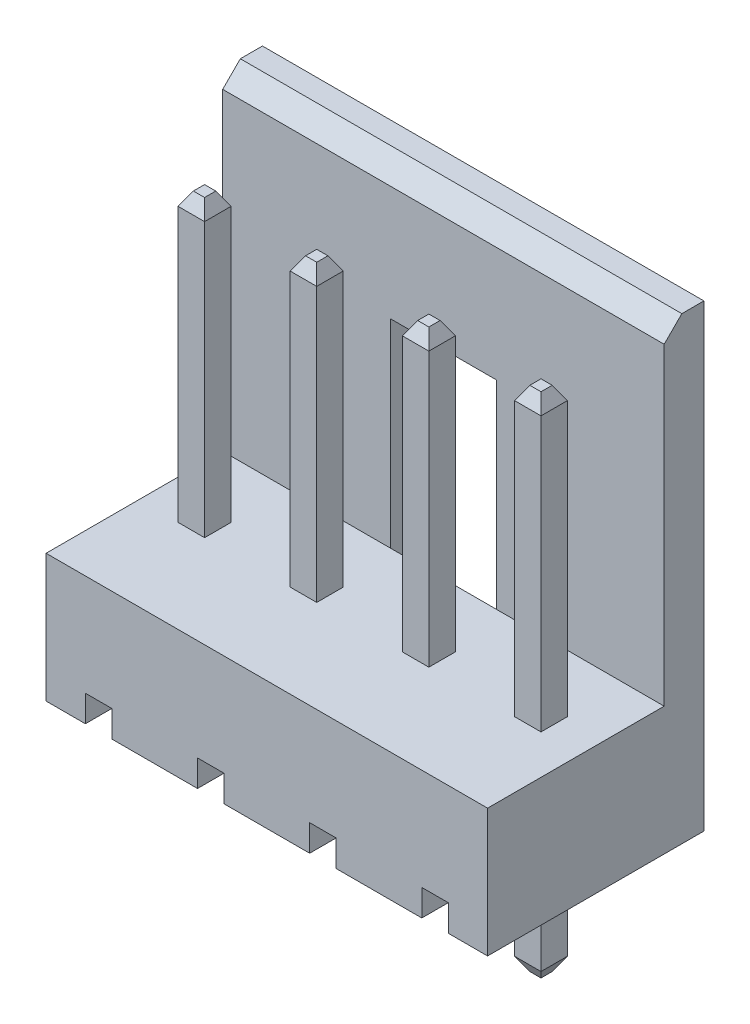
SolidWorks part; units mm, degrees
note: The reader was unsure of these and kept them because the rebuilt part matched: shared geometry of "Sketch2<2>".
ref_plane "Front Plane" through (0, 0, 0) normal (0, 0, 1) x (1, 0, 0)
ref_plane "Top Plane" through (0, 0, 0) normal (0, 1, 0) x (1, 0, 0)
ref_plane "Right Plane" through (0, 0, 0) normal (1, 0, 0) x (0, 0, -1)
sketch "Sketch1" plane through (0, 0, 0) normal (1, 0, 0) x (0, 0, -1)
  line L0 (0, 10.4) -> (-0.5, 10.4)
  line L1 (-0.5, 10.4) -> (-0.9, 10)
  line L2 (-0.9, 10) -> (-0.9, 2.9)
  line L3 (-0.9, 2.9) -> (-4.9, 2.9)
  line L4 (-4.9, 2.9) -> (-4.9, 0)
  line L5 (-4.9, 0) -> (0, 0)
  line L6 (0, 0) -> (0, 10.4)
  dimension "D1" = 10.4
  dimension "D2" = 4.9
  dimension "D3" = 2.9
  dimension "D4" = 4
  dimension "D5" = 45
  dimension "D6" = 0.5
extrude "Boss-Extrude1" add sketch "Sketch1" along normal mid plane 10
sketch "Sketch2" plane through (0, 2.9, 0) normal (0, 1, 0) x (1, 0, 0)
  line L1 (-4.11, -2.2) -> (-3.51, -2.2)
  line L2 (-4.11, -2.2) -> (-4.11, -2.8)
  line L3 (-4.11, -2.8) -> (-3.51, -2.8)
  line L4 (-3.51, -2.2) -> (-3.51, -2.8)
  line L16 (-1.57, -2.8) -> (-0.97, -2.8)
  line L17 (-0.97, -2.2) -> (-0.97, -2.8)
  line L18 (-1.57, -2.2) -> (-0.97, -2.2)
  line L19 (5, -4.9) -> (-5, -4.9) construction
  line L20 (-1.57, -2.2) -> (-1.57, -2.8)
  line L21 (0.97, -2.8) -> (1.57, -2.8)
  line L22 (1.57, -2.2) -> (1.57, -2.8)
  line L23 (0.97, -2.2) -> (1.57, -2.2)
  line L24 (0.97, -2.2) -> (0.97, -2.8)
  line L25 (3.51, -2.8) -> (4.11, -2.8)
  line L26 (4.11, -2.2) -> (4.11, -2.8)
  line L27 (3.51, -2.2) -> (4.11, -2.2)
  line L28 (3.51, -2.2) -> (3.51, -2.8)
  line L29 (-4.11, -2.8) -> (-1.57, -2.8) construction
  point P4 (-3.81, -2.2)
  point P21 (-4.11, -2.5)
  dimension "D1" = 0.6
  dimension "D3" = 4
  dimension "D4" = 2.4
  dimension "D2" = 3.81
  dimension "D5" = 2.54
extrude "Cut-Extrude1" cut sketch "Sketch2" against normal through all
extrude "Boss-Extrude2" add sketch "Sketch2<2>" along normal blind 6.5 and the other way blind 5 separate body contours L4 L3 L2 L1
sketch "Sketch2<2>" plane through (0, 2.9, 0) normal (0, 1, 0) x (1, 0, 0) same geometry as "Sketch2"
chamfer "Chamfer1" distance 0.3 angle 30 8 edges at (-3.81, -2.1, 2.8) (-3.51, -2.1, 2.5) (-3.81, -2.1, 2.2) (-4.11, -2.1, 2.5) (-3.81, 9.4, 2.2) (-3.51, 9.4, 2.5) (-3.81, 9.4, 2.8) (-4.11, 9.4, 2.5)
pattern_linear "LPattern1" count 4 spacing 2.54 along (1, 0, 0) of bodies 103
sketch "Sketch3" plane through (0, 0, 0) normal (0, 0, -1) x (-1, 0, 0)
  line L0 (-5, 0) -> (5, 0) construction
  line L1 (-1.2, 7.4) -> (1.2, 7.4)
  line L2 (-1.2, 7.4) -> (-1.2, 0)
  line L3 (-1.2, 0) -> (1.2, 0)
  line L4 (1.2, 7.4) -> (1.2, 0)
  dimension "D1" = 7.4
  dimension "D2" = 2.4
extrude "Cut-Extrude2" cut sketch "Sketch3" against normal up to surface (0.9 mm away) up to face at (0, 6.45, 0.9)
sketch "Sketch4" plane through (0, 0, 4.9) normal (0, 0, 1) x (1, 0, 0)
  line L0 (-4.11, -1.8) -> (-4.11, 9.1) construction
  line L1 (-4.11, 0.6) -> (-3.51, 0.6)
  line L2 (-4.11, 0.6) -> (-4.11, 0)
  line L3 (-4.11, 0) -> (-3.51, 0)
  line L4 (-3.51, 0.6) -> (-3.51, 0)
  line L5 (-1.57, 0.6) -> (-1.57, 0)
  line L6 (-1.57, 0) -> (-0.97, 0)
  line L7 (-0.97, 0.6) -> (-0.97, 0)
  line L8 (-1.57, 0.6) -> (-0.97, 0.6)
  line L9 (0.97, 0.6) -> (0.97, 0)
  line L10 (0.97, 0) -> (1.57, 0)
  line L11 (1.57, 0.6) -> (1.57, 0)
  line L12 (0.97, 0.6) -> (1.57, 0.6)
  line L13 (3.51, 0.6) -> (3.51, 0)
  line L14 (3.51, 0) -> (4.11, 0)
  line L15 (4.11, 0.6) -> (4.11, 0)
  line L16 (3.51, 0.6) -> (4.11, 0.6)
  line L17 (-4.11, 0.6) -> (-1.57, 0.6) construction
  dimension "D2" = 2.54
  dimension "D1" = 4
extrude "Cut-Extrude3" cut sketch "Sketch4" against normal through all
